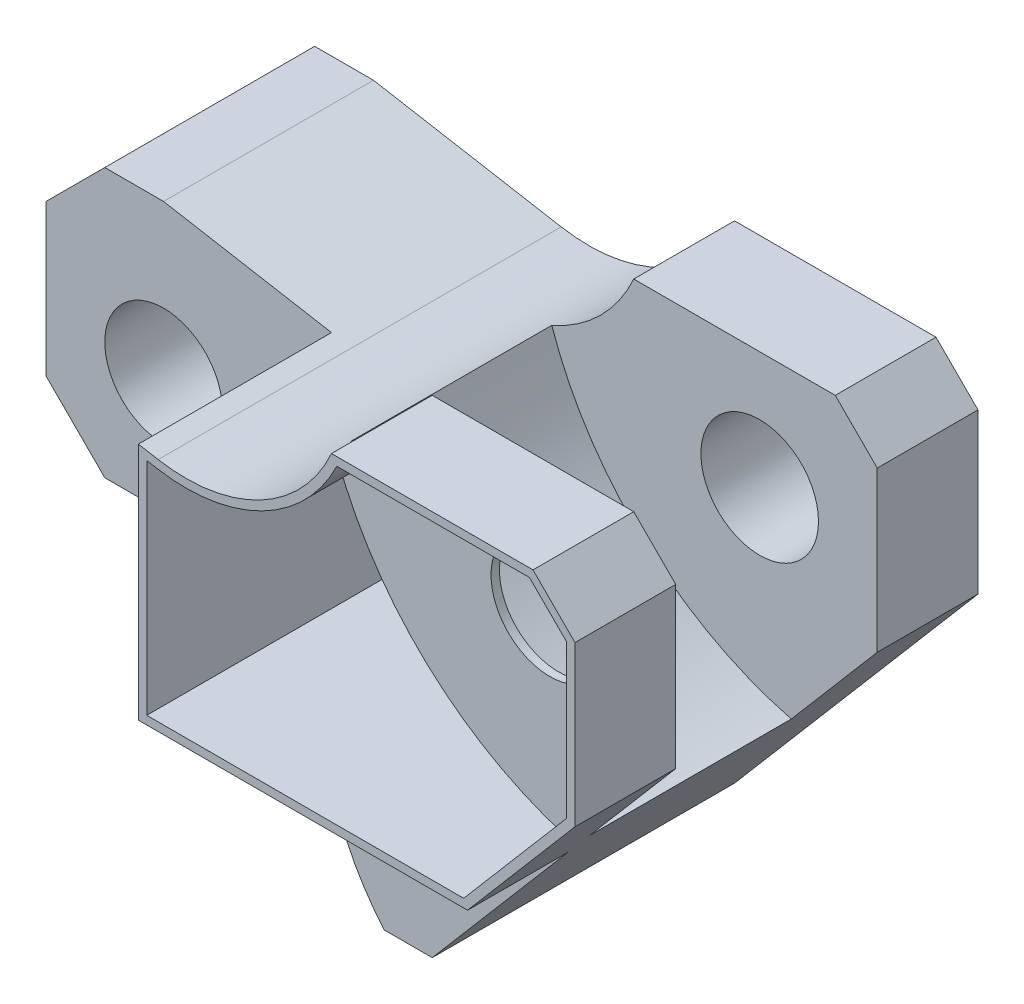
SolidWorks part; units mm, degrees
material "AISI 1020"
ref_plane "Front Plane" through (0, 0, 0) normal (0, 0, 1) x (1, 0, 0)
ref_plane "Top Plane" through (0, 0, 0) normal (0, 1, 0) x (1, 0, 0)
ref_plane "Right Plane" through (0, 0, 0) normal (1, 0, 0) x (0, 0, -1)
sketch "Sketch1" plane through (0, 0, 0) normal (0, 0, 1) x (1, 0, 0)
  line L0 (-72, -18) -> (-72, 0)
  line L1 (-72, 0) -> (-65, 7)
  line L2 (-65, 7) -> (-58, 7)
  line L3 (-58, 7) -> (-35.6386, 3.0571)
  line L4 (-15, 14) -> (9, 14)
  line L5 (9, 14) -> (14, 9)
  line L6 (14, 9) -> (14, -10)
  line L7 (14, -10) -> (-15, -44)
  line L8 (-15, -44) -> (-20.703, -44)
  line L9 (-32.4245, -25) -> (-65, -25)
  line L10 (-65, -25) -> (-72, -18)
  line L11 (-38, 3.4735) -> (-38, -25)
  line L12 (-38, -25) -> (1.2059, -25)
  arc A0 (-35.6386, 3.0571) -> (-15, 14) centre (-32.3393, 21.7684) ccw
  arc A1 (-20.703, -44) -> (-27.4788, -29.2647) centre (1.2059, -25) cw
  arc A2 (-27.4788, -29.2647) -> (-32.4245, -25) centre (-32.4245, -30) ccw
  circle A3 centre (-58, -11) radius 7
  circle A4 centre (0, 0) radius 7
  arc A5 (-24.7631, 4.3443) -> (3.7647, -22) centre (14, 17.7019) ccw
  dimension "D12" = 29
  dimension "D14" = 14
  dimension "D15" = 14
  dimension "D20" = 5
  dimension "D21" = 19
  dimension "D27" = 41
  dimension "D1" = 32
  dimension "D2" = 14
  dimension "D3" = 45
  dimension "D4" = 10
  dimension "D5" = 29
  dimension "D6" = 14
  dimension "D7" = 45
  dimension "D8" = 5
  dimension "D9" = 14
  dimension "D10" = 24
  dimension "D11" = 58
  dimension "D13" = 14
  dimension "D16" = 7
  dimension "D17" = 14
  dimension "D18" = 45
  dimension "D19" = 7
  dimension "D22" = 29
  dimension "D23" = 52
  dimension "D24" = 86
  dimension "D25" = 36
  dimension "D26" = 19
extrude "Boss-Extrude1" add sketch "Sketch1" along normal blind 25 contours L11 L3 L2 L1 L0 L10 L9 A3 region at (-71.5331, -9, 0)
extrude "Boss-Extrude2" add sketch "Sketch1<3>" along normal blind 24 from offset 12 separate body contours A5 A0 L3 L11 L9 L12 L7 region at (-23.9468, -13.7236, 0)
sketch "Sketch1<3>" plane through (0, 0, 0) normal (0, 0, 1) x (1, 0, 0) same geometry as "Sketch1"
extrude "Boss-Extrude3" add sketch "Sketch1<4>" along normal blind 12 contours A0 A5 L7 L6 L5 L4 A4 | A5 A0 L3 L11 L9 L12 L7 region at (-23.9468, -13.7236, 0) region at (-13.4568, -12.0306, 0)
sketch "Sketch1<4>" plane through (0, 0, 0) normal (0, 0, 1) x (1, 0, 0) same geometry as "Sketch1"
extrude "Boss-Extrude6" add sketch "Sketch1<7>" along normal blind 12 from offset 36 contours A0 A5 L7 L6 L5 L4 A4 | A5 A0 L3 L11 L9 L12 L7 region at (-23.9468, -13.7236, 0) region at (-13.4568, -12.0306, 0)
sketch "Sketch1<7>" plane through (0, 0, 0) normal (0, 0, 1) x (1, 0, 0) same geometry as "Sketch1"
shell "Shell7" thickness 1 removed face at (7, 0, 48)
extrude "Boss-Extrude7" add sketch "Sketch1<8>" along normal blind 36 contours A2 A1 L8 L7 L12 region at (-15.9101, -32.4639, 0)
sketch "Sketch1<8>" plane through (0, 0, 0) normal (0, 0, 1) x (1, 0, 0) same geometry as "Sketch1"
combine bodies "Combine1" operation type add bodies to combine 107 106
sketch "Sketch2" plane through (0, 0, 37) normal (0, 0, 1) x (1, 0, 0)
  circle A0 centre (0, 0) radius 9.6957
extrude "Cut-Extrude2" cut sketch "Sketch2" along normal through all
